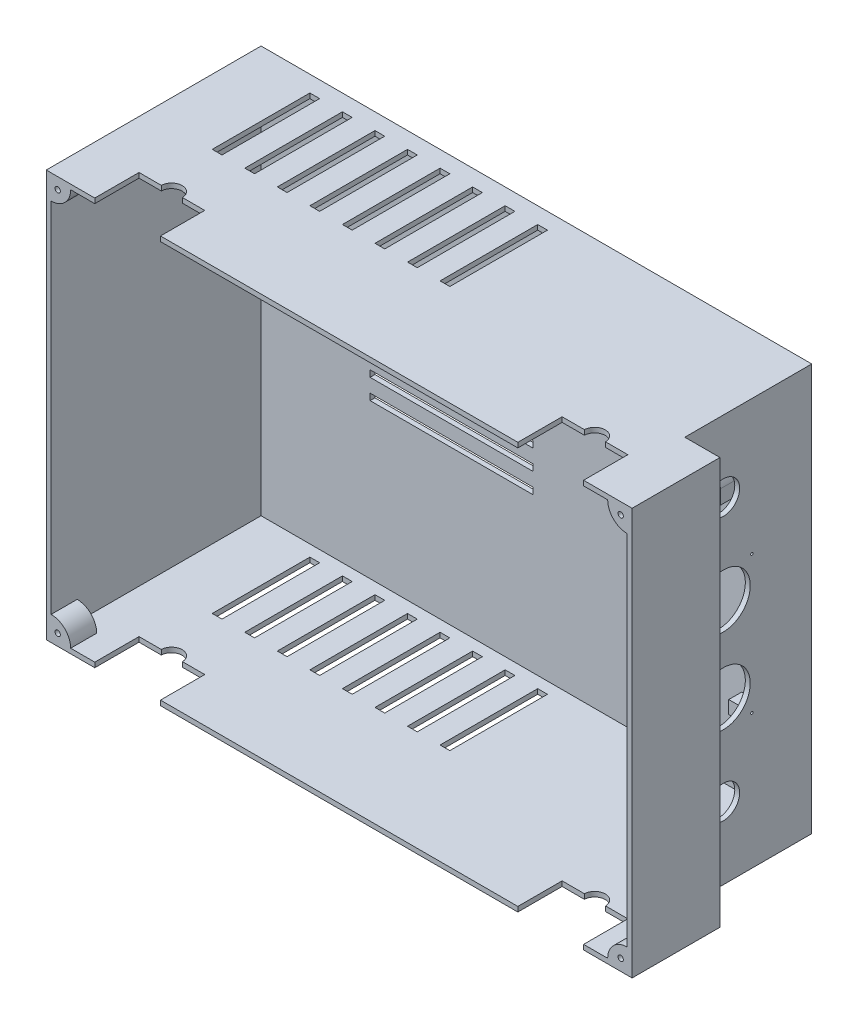
SolidWorks part; units mm, degrees
ref_plane "前视基准面" through (0, 0, 0) normal (0, 0, 1) x (1, 0, 0)
ref_plane "上视基准面" through (0, 0, 0) normal (0, 1, 0) x (1, 0, 0)
ref_plane "右视基准面" through (0, 0, 0) normal (1, 0, 0) x (0, 0, -1)
sketch "草图2" plane through (0, 0, 0) normal (0, 0, 1) x (1, 0, 0)
  line L1 (-90, 62.5) -> (90, 62.5)
  line L2 (-90, 62.5) -> (-90, -62.5)
  line L3 (-90, -62.5) -> (90, -62.5)
  line L4 (90, 62.5) -> (90, -62.5)
  line L5 (-90, 62.5) -> (90, -62.5) construction
  line L6 (-90, -62.5) -> (90, 62.5) construction
  point P0 (0, 0)
  dimension "D1" = 180
  dimension "D2" = 125
extrude "凸台-拉伸1" add sketch "草图2" along normal blind 66
sketch "草图4" plane through (90, 0, 0) normal (1, 0, 0) x (0, 0, -1)
  line L0 (-39, -62.5) -> (-39, 62.5)
  line L1 (-66, 61.5) -> (-66, -61.5) construction
  line L2 (-66, 62.5) -> (0, 62.5) construction
  line L4 (0, -62.5) -> (0, 62.5)
  line L6 (-66, 62.5) -> (-66, -62.5)
  line L9 (0, 62.5) -> (-39, 62.5)
  line L11 (-39, -62.5) -> (0, -62.5)
  line L14 (0, -62.5) -> (0, 62.5)
  line L15 (0, 62.5) -> (-66, 62.5)
  line L16 (-66, -62.5) -> (0, -62.5)
  dimension "D2" = 27
  dimension "D1" = 0
extrude "切除-拉伸2" cut sketch "草图4" against normal offset from surface (10.8 mm away) 2
shell "抽壳1" thickness 1.5 removed face at (0, 0, 66)
sketch "草图6" plane through (79.2, 0, 0) normal (1, 0, 0) x (0, 0, -1)
  line L1 (-16.4, -23.15) -> (-20.4, -23.15)
  line L2 (-16.4, -23.15) -> (-16.4, -19.15)
  line L3 (-16.4, -19.15) -> (-20.4, -19.15)
  line L4 (-20.4, -23.15) -> (-20.4, -19.15)
  line L5 (-33.9, -23.15) -> (-37.9, -23.15)
  line L6 (-33.9, -23.15) -> (-33.9, -19.15)
  line L7 (-33.9, -19.15) -> (-37.9, -19.15)
  line L8 (-37.9, -23.15) -> (-37.9, -19.15)
  line L9 (-33.9, 19.15) -> (-37.9, 19.15)
  line L10 (-33.9, 19.15) -> (-33.9, 23.15)
  line L11 (-33.9, 23.15) -> (-37.9, 23.15)
  line L12 (-37.9, 19.15) -> (-37.9, 23.15)
  line L13 (-16.4, 19.15) -> (-20.4, 19.15)
  line L14 (-16.4, 19.15) -> (-16.4, 23.15)
  line L15 (-16.4, 23.15) -> (-20.4, 23.15)
  line L16 (-20.4, 19.15) -> (-20.4, 23.15)
  circle A0 centre (-18.4, 21.15) radius 1 construction
  circle A1 centre (-35.9, 21.15) radius 1 construction
  circle A2 centre (-18.4, -21.15) radius 1 construction
  circle A3 centre (-35.9, -21.15) radius 1 construction
  dimension "D10" = 2
  dimension "D3" = 2
  dimension "D6" = 2
  dimension "D9" = 2
  dimension "D14" = 2
  dimension "D2" = 2
  dimension "D4" = 2
  dimension "D5" = 4
  dimension "D7" = 4
  dimension "D8" = 4
  dimension "D11" = 4
  dimension "D12" = 4
  dimension "D13" = 2
  dimension "D15" = 4
  dimension "D16" = 4
extrude "凸台-拉伸2" add sketch "草图6" against normal up to surface (5.1 mm away)
sketch "草图7" plane through (79.2, 0, 0) normal (1, 0, 0) x (0, 0, -1)
  circle A0 centre (-27.15, -13) radius 8.25
  circle A1 centre (-27.15, 13) radius 8.25
  circle A2 centre (-18.4, -21.15) radius 0.375
  circle A3 centre (-18.4, 21.15) radius 0.375
  circle A4 centre (-35.9, 21.15) radius 0.375
  circle A5 centre (-35.9, -21.15) radius 0.375
  circle A6 centre (-27.15, 40.5) radius 4.75 construction
  circle A7 centre (-27.15, 40.5) radius 5
  circle A9 centre (-27.15, -40.5) radius 5
  circle A10 centre (-27.15, 13) radius 8 construction
  circle A13 centre (-27.15, -13) radius 8 construction
  circle A14 centre (-18.4, 21.15) radius 1 construction
  circle A15 centre (-35.9, 21.15) radius 1 construction
  circle A16 centre (-35.9, -21.15) radius 1 construction
  circle A17 centre (-18.4, -21.15) radius 1 construction
  dimension "D1" = 0.75
  dimension "D2" = 0.25
  dimension "D3" = 0.25
extrude "切除-拉伸3" cut sketch "草图7" against normal up to next
sketch "草图8" plane through (0, -62.5, 0) normal (0, -1, 0) x (1, 0, 0)
  line L0 (-60, 35) -> (-57, 35)
  line L5 (-60, 35) -> (-60, 5)
  line L26 (-90, 66) -> (-90, 0) construction
  line L27 (-70, 35) -> (-67, 35)
  line L28 (-70, 35) -> (-70, 5)
  line L29 (-70, 5) -> (-67, 5)
  line L30 (-67, 35) -> (-67, 5)
  line L31 (-90, 0) -> (79.2, 0) construction
  line L32 (-60, 5) -> (-57, 5)
  line L33 (-57, 35) -> (-57, 5)
  line L34 (-50, 35) -> (-47, 35)
  line L35 (-50, 35) -> (-50, 5)
  line L36 (-50, 5) -> (-47, 5)
  line L37 (-47, 35) -> (-47, 5)
  line L38 (-40, 35) -> (-37, 35)
  line L39 (-40, 35) -> (-40, 5)
  line L40 (-40, 5) -> (-37, 5)
  line L41 (-37, 35) -> (-37, 5)
  line L42 (-30, 35) -> (-27, 35)
  line L43 (-30, 35) -> (-30, 5)
  line L44 (-30, 5) -> (-27, 5)
  line L45 (-27, 35) -> (-27, 5)
  line L46 (-20, 35) -> (-17, 35)
  line L47 (-20, 35) -> (-20, 5)
  line L48 (-20, 5) -> (-17, 5)
  line L49 (-17, 35) -> (-17, 5)
  line L50 (-10, 35) -> (-7, 35)
  line L51 (-10, 35) -> (-10, 5)
  line L52 (-10, 5) -> (-7, 5)
  line L53 (-7, 35) -> (-7, 5)
  line L54 (0, 35) -> (3, 35)
  line L55 (0, 35) -> (0, 5)
  line L56 (0, 5) -> (3, 5)
  line L57 (3, 35) -> (3, 5)
  dimension "D1" = 3
  dimension "D2" = 20
  dimension "D3" = 30
  dimension "D4" = 5
extrude "切除-拉伸4" cut sketch "草图8" against normal up to surface (125 mm away) and the other way through all up to face at (26.4, 62.5, 35)
sketch "草图9" plane through (0, 0, 66) normal (0, 0, 1) x (1, 0, 0)
  line L1 (-88.5, 61) -> (-82.5, 61)
  line L2 (-88.5, 61) -> (-88.5, 55)
  line L5 (0, 0) -> (0, 36.715) construction
  line L6 (0, 0) -> (38.7304, 0) construction
  line L7 (-88.5, -61) -> (-88.5, -55)
  line L8 (-88.5, -61) -> (-82.5, -61)
  line L9 (88.5, -61) -> (82.5, -61)
  line L10 (88.5, -61) -> (88.5, -55)
  line L11 (88.5, 61) -> (88.5, 55)
  line L12 (88.5, 61) -> (82.5, 61)
  circle A0 centre (-86.5, 59) radius 0.825
  arc A1 (-82.5, 61) -> (-88.5, 55) centre (-88.5, 61) cw
  arc A2 (-82.5, -61) -> (-88.5, -55) centre (-88.5, -61) ccw
  circle A3 centre (-86.5, -59) radius 0.825
  circle A4 centre (86.5, -59) radius 0.825
  arc A5 (82.5, -61) -> (88.5, -55) centre (88.5, -61) cw
  arc A6 (82.5, 61) -> (88.5, 55) centre (88.5, 61) ccw
  circle A7 centre (86.5, 59) radius 0.825
  dimension "D1" = 1.65
  dimension "D2" = 2
  dimension "D3" = 2
  dimension "D4" = 6
extrude "凸台-拉伸3" add sketch "草图9" against normal blind 8
sketch "草图10" plane through (0, 0, 1.5) normal (0, 0, 1) x (1, 0, 0)
  line L0 (77.7, -61) -> (77.7, 61) construction
  line L1 (77.7, 50.5757) -> (70.5117, 50.5757)
  line L2 (77.7, 50.5757) -> (77.7, 61)
  line L3 (77.7, 61) -> (70.5117, 61)
  line L4 (70.5117, 50.5757) -> (70.5117, 61)
  line L5 (82.5, 61) -> (-82.5, 61) construction
  line L7 (62.5257, 50.5757) -> (55.3374, 50.5757)
  line L8 (62.5257, 50.5757) -> (62.5257, 61)
  line L9 (62.5257, 61) -> (55.3374, 61)
  line L10 (55.3374, 50.5757) -> (55.3374, 61)
  line L11 (62.5257, 22.2546) -> (55.3374, 22.2546)
  line L12 (62.5257, 22.2546) -> (62.5257, 29.6276)
  line L13 (62.5257, 29.6276) -> (55.3374, 29.6276)
  line L14 (55.3374, 22.2546) -> (55.3374, 29.6276)
  line L15 (77.7, 61) -> (-88.5, 61) construction
  line L16 (77.7, 22.2546) -> (70.5117, 22.2546)
  line L17 (77.7, 22.2546) -> (77.7, 29.6276)
  line L18 (77.7, 29.6276) -> (70.5117, 29.6276)
  line L19 (70.5117, 22.2546) -> (70.5117, 29.6276)
  arc A0 (74.0117, 27.2546) -> (74.0117, 25.2546) centre (74.0117, 26.2546) ccw construction
  arc A1 (59.0257, 25.1276) -> (59.0257, 27.1276) centre (59.0257, 26.1276) ccw construction
  arc A2 (59.0257, 27.1276) -> (59.0257, 25.1276) centre (59.0257, 26.1276) ccw construction
  arc A4 (74.1387, 53.5757) -> (74.1387, 55.5757) centre (74.1387, 54.5757) ccw construction
  circle A5 centre (74.1387, 54.5757) radius 0.825
  circle A6 centre (59.1527, 54.5757) radius 0.825
  circle A7 centre (59.0257, 26.1276) radius 0.825
  circle A8 centre (74.0117, 26.2546) radius 0.825
  dimension "D7" = 1.65
  dimension "D6" = 1.65
  dimension "D8" = 1.65
  dimension "D9" = 1.65
  dimension "D1" = 4
  dimension "D2" = 3.5
  dimension "D3" = 3.5
  dimension "D4" = 3.5
  dimension "D5" = 4
extrude "开关螺孔凸台-拉伸4" add sketch "草图10" along normal up to surface (9.8999 mm away)
sketch "草图11" plane through (0, 0, 0) normal (0, 0, -1) x (-1, 0, 0)
  circle A0 centre (-66.7727, 36.1607) radius 6.1
  circle A5 centre (-65.4947, 49.2417) radius 2.6
  dimension "D1" = 12.2
  dimension "D2" = 5.2
extrude "切除-拉伸5" cut sketch "草图11" against normal up to next
fillet "圆角1" radius 3 4 edges at (62.5257, 29.6276, 6.45) (62.5257, 50.5757, 6.45) (70.5117, 29.6276, 6.45) (70.5117, 50.5757, 6.45)
sketch "草图12" plane through (0, 62.5, 0) normal (0, 1, 0) x (1, 0, 0)
  line L0 (-55, -66) -> (55, -66) construction
  line L1 (-75.1, -52.4) -> (-68.2485, -52.4)
  line L2 (-75.1, -52.4) -> (-75.1, -66)
  line L3 (-75.1, -66) -> (-54.9, -66)
  line L4 (-54.9, -52.4) -> (-54.9, -66)
  line L5 (-55, -52.5) -> (-55, -66) construction
  line L6 (-61.75, -52.5) -> (-55, -52.5) construction
  line L7 (-75, -52.5) -> (-75, -66) construction
  line L8 (-61.7515, -52.4) -> (-54.9, -52.4)
  line L9 (75, -66) -> (89, -66) construction
  line L10 (54.9, -52.4) -> (61.7515, -52.4)
  line L11 (54.9, -52.4) -> (54.9, -66)
  line L12 (54.9, -66) -> (75.1, -66)
  line L13 (75.1, -52.4) -> (75.1, -66)
  line L14 (75, -52.5) -> (75, -66) construction
  line L15 (68.25, -52.5) -> (75, -52.5) construction
  line L16 (55, -52.5) -> (55, -66) construction
  line L17 (68.2485, -52.4) -> (75.1, -52.4)
  arc A0 (-68.2485, -52.4) -> (-61.7515, -52.4) centre (-65, -52.5) cw
  arc A3 (-68.25, -52.5) -> (-61.75, -52.5) centre (-65, -52.5) ccw construction
  arc A4 (61.7515, -52.4) -> (68.2485, -52.4) centre (65, -52.5) cw
  circle A5 centre (65, -52.5) radius 3.25 construction
  arc A6 (61.75, -52.5) -> (68.25, -52.5) centre (65, -52.5) ccw construction
  dimension "D1" = 0.1
  dimension "D2" = 0.1
  dimension "D3" = 0.1
  dimension "D4" = 0.1
  dimension "D5" = 0.1
  dimension "D6" = 0.1
extrude "切除-拉伸6" cut sketch "草图12" against normal up to surface (125 mm away) up to face at (-68.5, -62.5, 20)
sketch "草图13" plane through (0, 0, 0) normal (0, 0, -1) x (-1, 0, 0)
  line L0 (55, -7.4172) -> (5, -7.4172)
  line L1 (55, -13.6172) -> (5, -13.6172)
  line L2 (55, -13.6172) -> (55, -11.6172)
  line L3 (55, -11.6172) -> (5, -11.6172)
  line L4 (5, -13.6172) -> (5, -11.6172)
  line L5 (90, 62.5) -> (90, -62.5) construction
  line L6 (55, -7.4172) -> (55, -5.4172)
  line L7 (55, -5.4172) -> (5, -5.4172)
  line L8 (5, -7.4172) -> (5, -5.4172)
  line L9 (55, -1.2172) -> (5, -1.2172)
  line L10 (55, -1.2172) -> (55, 0.7828)
  line L11 (55, 0.7828) -> (5, 0.7828)
  line L12 (5, -1.2172) -> (5, 0.7828)
  line L13 (55, 4.9828) -> (5, 4.9828)
  line L14 (55, 4.9828) -> (55, 6.9828)
  line L15 (55, 6.9828) -> (5, 6.9828)
  line L16 (5, 4.9828) -> (5, 6.9828)
  line L17 (55, 11.1828) -> (5, 11.1828)
  line L18 (55, 11.1828) -> (55, 13.1828)
  line L19 (55, 13.1828) -> (5, 13.1828)
  line L20 (5, 11.1828) -> (5, 13.1828)
  dimension "D1" = 2
  dimension "D2" = 50
  dimension "D3" = 35
extrude "切除-拉伸7" cut sketch "草图13" against normal up to next
